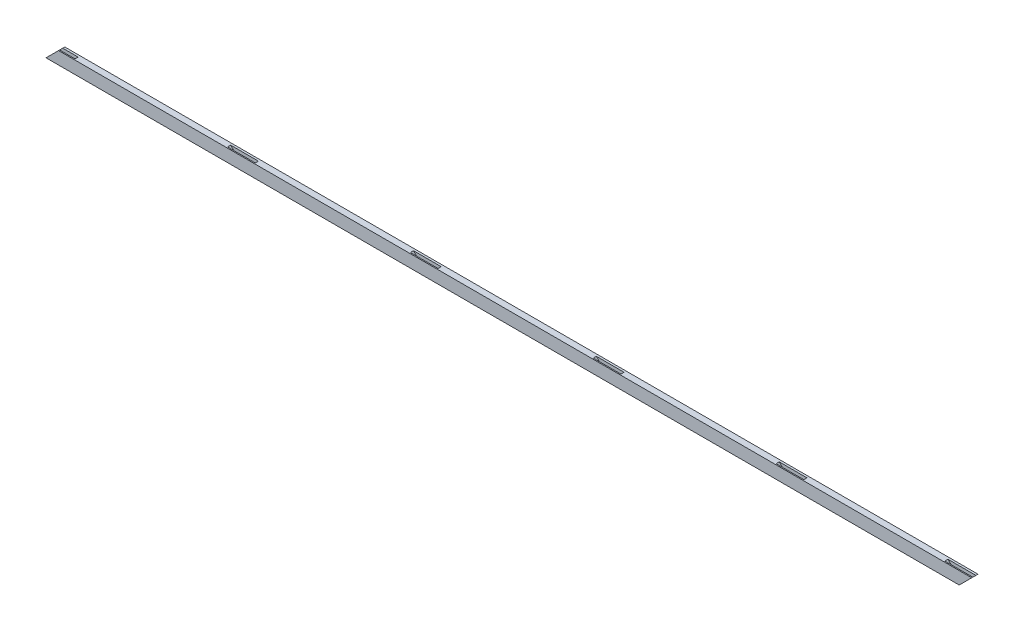
SolidWorks part; units mm, degrees
ref_plane "前视基准面" through (0, 0, 0) normal (0, 0, 1) x (1, 0, 0)
ref_plane "上视基准面" through (0, 0, 0) normal (0, 1, 0) x (1, 0, 0)
ref_plane "右视基准面" through (0, 0, 0) normal (1, 0, 0) x (0, 0, -1)
sketch "草图1" plane through (0, 0, 0) normal (0, 0, 1) x (1, 0, 0)
  line L0 (-12, -12) -> (12, 12)
  line L1 (12, 12) -> (1760, 12)
  line L2 (1760, 12) -> (1736, -12)
  line L3 (1736, -12) -> (-12, -12)
  point P3 (0, 0)
  dimension "D1" = 1772
  dimension "D2" = 45
  dimension "D3" = 45
  dimension "D4" = 24
extrude "凸台-拉伸1" add sketch "草图1" along normal blind 12
sketch "草图2" plane through (0, -12, 0) normal (0, -1, 0) x (1, 0, 0)
  line L0 (1390, 10) -> (1390, 4)
  line L1 (1390, 4) -> (1430, 4)
  line L2 (1430, 4) -> (1430, 10)
  line L3 (1430, 10) -> (1390, 10)
  line L4 (-12, 0) -> (1736, 0) construction
  point P6 (1410, 10)
  dimension "D1" = 40
  dimension "D2" = 6
  dimension "D3" = 4
  dimension "D4" = 350
extrude "切除-拉伸1" cut sketch "草图2" against normal blind 6.5
draft "拔模1" type of draft neutral plane draft angle 45 faces to draft 2 face at (1430, -8.75, 7) face at (1390, -8.75, 7) neutral plane through (0, -5.5, 0) neutral plane normal (0, -1, 0) parameters "D1"=45
mirror "镜向1" about plane through (0, 0, 0) normal (0, 1, 0) of face at (1410, -8.75, 10) of face at (1433.25, -8.75, 7) of face at (1410, -8.75, 4) of face at (1386.75, -8.75, 7) of face at (1410, -5.5, 7)
pattern_linear "阵列(线性)2" count 4 spacing 350 along (-1, 0, 0) of face at (1410, -8.75, 10) of face at (1433.25, -8.75, 7) of face at (1410, -5.5, 7) of face at (1386.75, -8.75, 7) of face at (1410, -8.75, 4) of face at (1433.25, 8.75, 7) of face at (1410, 5.5, 7) of face at (1410, 8.75, 4) of face at (1410, 8.75, 10) of face at (1386.75, 8.75, 7)
sketch "草图3" plane through (0, 0, 12) normal (0, 0, 1) x (1, 0, 0)
  line L0 (1706.5, 12) -> (1713, 5.5)
  line L1 (1760, 12) -> (12, 12) construction
  line L2 (1713, 5.5) -> (1753.5, 5.5)
  line L3 (1736, -12) -> (1760, 12) construction
  line L4 (1753.5, 5.5) -> (1760, 12)
  line L5 (1760, 12) -> (1706.5, 12)
  line L6 (1706.5, -12) -> (1713, -5.5)
  line L7 (-12, -12) -> (1736, -12) construction
  line L8 (1713, -5.5) -> (1742.5, -5.5)
  line L9 (1742.5, -5.5) -> (1736, -12)
  line L10 (1736, -12) -> (1706.5, -12)
  line L11 (12, 12) -> (5.5, 5.5)
  line L12 (12, 12) -> (-12, -12) construction
  line L13 (5.5, 5.5) -> (35, 5.5)
  line L14 (35, 5.5) -> (41.5, 12)
  line L15 (41.5, 12) -> (12, 12)
  line L16 (41.5, -12) -> (35, -5.5)
  line L17 (35, -5.5) -> (-5.5, -5.5)
  line L18 (-5.5, -5.5) -> (-12, -12)
  line L19 (-12, -12) -> (41.5, -12)
  dimension "D1" = 47
  dimension "D2" = 23
  dimension "D3" = 6.5
  dimension "D4" = 6.5
  dimension "D5" = 45
  dimension "D6" = 23
  dimension "D7" = 47
  dimension "D8" = 6.5
  dimension "D9" = 6.5
  dimension "D10" = 45
  dimension "D11" = 45
extrude "切除-拉伸2" cut sketch "草图3" against normal blind 6 from offset 2 offset against normal yes
